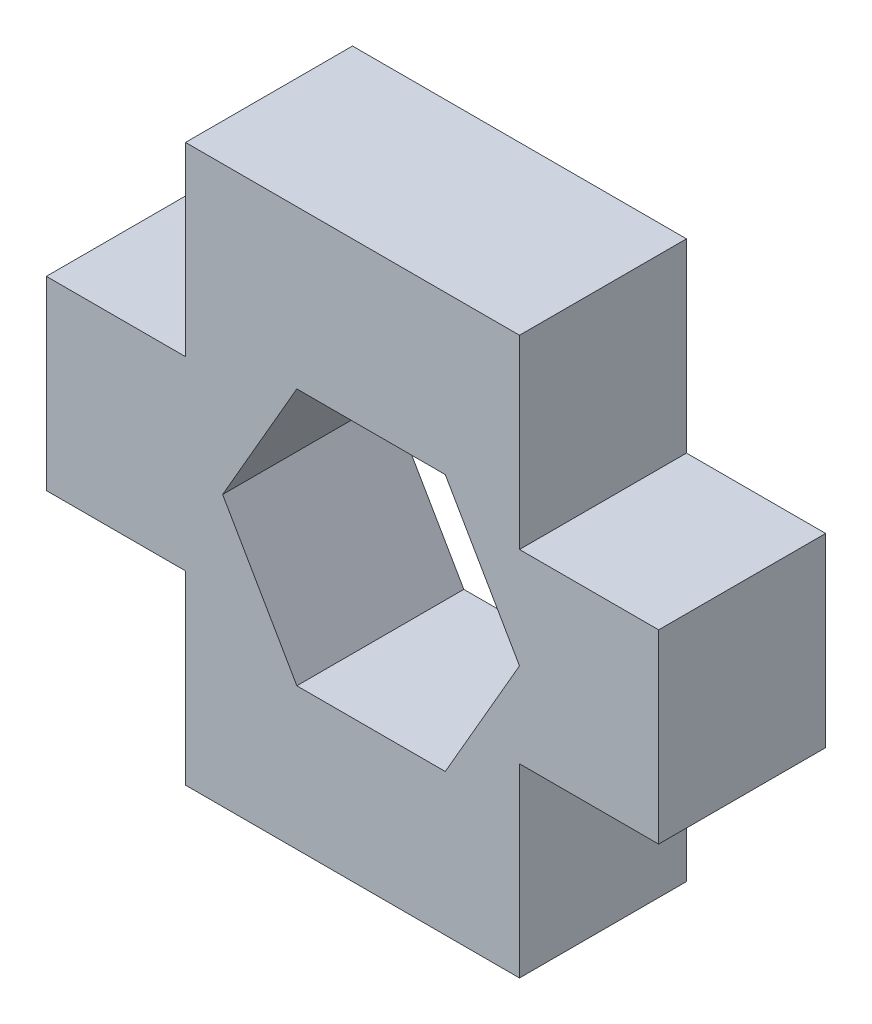
SolidWorks part; units mm, degrees
ref_plane "Front Plane" through (0, 0, 0) normal (0, 0, 1) x (1, 0, 0)
ref_plane "Top Plane" through (0, 0, 0) normal (0, 1, 0) x (1, 0, 0)
ref_plane "Right Plane" through (0, 0, 0) normal (1, 0, 0) x (0, 0, -1)
sketch "Sketch1" plane through (0, 0, 0) normal (0, 0, 1) x (1, 0, 0)
  line L0 (0, 0) -> (7.2, 0)
  line L1 (7.2, 0) -> (7.2, 4)
  line L2 (7.2, 4) -> (10.2, 4)
  line L3 (10.2, 4) -> (10.2, 8)
  line L4 (7.2, 8) -> (10.2, 8)
  line L5 (7.2, 8) -> (7.2, 12)
  line L6 (7.2, 12) -> (0, 12)
  line L7 (0, 12) -> (0, 8)
  line L8 (0, 8) -> (-3, 8)
  line L9 (-3, 8) -> (-3, 4)
  line L10 (-3, 4) -> (0, 4)
  line L11 (0, 4) -> (0, 0)
  line L14 (7.2, 5.8268) -> (5.6, 8.5981)
  line L15 (5.6, 8.5981) -> (2.4, 8.5981)
  line L16 (2.4, 8.5981) -> (0.8, 5.8268)
  line L17 (0.8, 5.8268) -> (2.4, 3.0555)
  line L18 (2.4, 3.0555) -> (5.6, 3.0555)
  line L19 (5.6, 3.0555) -> (7.2, 5.8268)
  dimension "D4" = 7.2
  dimension "D1" = 3
  dimension "D2" = 4
  dimension "D3" = 3.2
  dimension "D5" = 2.4
  dimension "D6" = 3.0555
  dimension "D7" = 5.8268
extrude "Boss-Extrude1" add sketch "Sketch1" along normal blind 3.6
sketch "Sketch2" [suppressed] plane through (-3, 0, 0) normal (-1, 0, 0) x (0, 0, 1)
  line L0 (2, 0) -> (2, 7) construction
  line L1 (4, 4) -> (4, 5) construction
  line L2 (4, 4) -> (5, 4) construction
  line L3 (0, 4) -> (-1, 4) construction
  line L4 (0, 4) -> (0, 5) construction
  line L5 (0, 6) -> (3.7, 6) construction
  line L6 (0, 8) -> (0, 4) construction
  line L7 (0, 8) -> (0, 7) construction
  line L8 (0, 8) -> (-1, 8) construction
  line L9 (4, 8) -> (5, 8) construction
  line L10 (4, 8) -> (4, 7) construction
  arc A0 (4, 5) -> (5, 4) centre (5, 5) ccw construction
  arc A1 (0, 5) -> (-1, 4) centre (-1, 5) cw construction
  arc A2 (0, 7) -> (-1, 8) centre (-1, 7) ccw construction
  arc A3 (4, 7) -> (5, 8) centre (5, 7) cw construction
  dimension "D1" = 1
  dimension "D2" = 1
  dimension "D3" = 4
  dimension "D4" = 4
  dimension "D6" = 4
sketch "Sketch3" plane through (0, 0, 3.6) normal (0, 0, 1) x (1, 0, 0)
  line L0 (2.4, 3.0555) -> (5.6, 8.5981) construction
  line L1 (2.4, 8.5981) -> (5.6, 3.0555) construction
  line L3 (2.4, 8.5981) -> (0.8, 5.8268)
  line L4 (0.8, 5.8268) -> (2.4, 3.0555)
  line L5 (2.4, 3.0555) -> (5.6, 3.0555)
  line L6 (5.6, 3.0555) -> (7.2, 5.8268)
  line L7 (7.2, 5.8268) -> (5.6, 8.5981)
  line L8 (5.6, 8.5981) -> (2.4, 8.5981)
  circle A0 centre (4, 5.8268) radius 2.7713 construction
extrude "Cut-Extrude1" [suppressed] cut sketch "Sketch3" against normal through all both and the other way through all
equation "\"D4@Sketch1\"= 8 - \"tol2@parametersSketch@prostheticParameters.SLDPRT\" * 2"
equation "\"D1@Boss-Extrude1\"=4 - \"tol2@parametersSketch@prostheticParameters.SLDPRT\""
